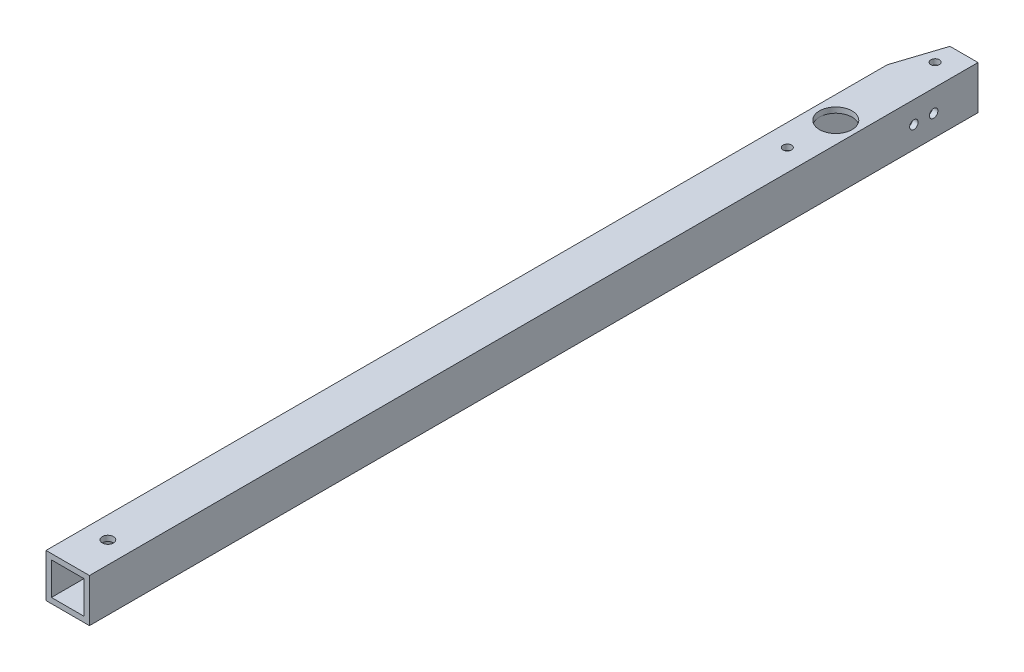
SolidWorks part; units mm, degrees
ref_plane "Front Plane" through (0, 0, 0) normal (0, 0, 1) x (1, 0, 0)
ref_plane "Top Plane" through (0, 0, 0) normal (0, 1, 0) x (1, 0, 0)
ref_plane "Right Plane" through (0, 0, 0) normal (1, 0, 0) x (0, 0, -1)
sketch "Sketch1" plane through (0, 0, 0) normal (0, 0, 1) x (1, 0, 0)
  line L0 (-9.525, 9.525) -> (9.525, 9.525)
  line L2 (-12.7, 12.7) -> (12.7, 12.7)
  line L3 (-12.7, 12.7) -> (-12.7, -12.7)
  line L4 (-12.7, -12.7) -> (12.7, -12.7)
  line L5 (12.7, 12.7) -> (12.7, -12.7)
  line L10 (9.525, 9.525) -> (9.525, -9.525)
  line L11 (-9.525, -9.525) -> (9.525, -9.525)
  line L12 (-9.525, 9.525) -> (-9.525, -9.525)
  point P12 (0, 12.7)
  point P14 (12.7, 0)
  dimension "Wall Thickness" = 3.175
  dimension "Outside Width" = 25.4
  dimension "Outside Height" = 25.4
  dimension "Inside Height" = 19.05
  dimension "Inside Width" = 19.05
sketch "Sketch2" plane through (0, 0, 0) normal (1, 0, 0) x (0, 0, -1)
  line L0 (266.7, 0) -> (-266.7, 0)
  point P4 (0, 0)
  point P7 (-266.7, 0)
  point P10 (266.7, 0)
  dimension "Length" = 533.4
sketch "Sketch3" plane through (0, 0, 0) normal (0, 0, 1) x (1, 0, 0)
  line L21 (12.7, 12.7) -> (-12.7, 12.7)
  line L22 (12.7, -12.7) -> (12.7, 12.7)
  line L23 (-12.7, -12.7) -> (12.7, -12.7)
  line L24 (-12.7, 12.7) -> (-12.7, -12.7)
  line L25 (12.7, 12.7) -> (-12.7, 12.7)
  line L26 (12.7, -12.7) -> (12.7, 12.7)
  line L27 (-12.7, -12.7) -> (12.7, -12.7)
  line L28 (-12.7, 12.7) -> (-12.7, -12.7)
  line L29 (9.525, 9.525) -> (-9.525, 9.525)
  line L30 (9.525, -9.525) -> (9.525, 9.525)
  line L31 (-9.525, -9.525) -> (9.525, -9.525)
  line L32 (-9.525, 9.525) -> (-9.525, -9.525)
  line L33 (9.525, 9.525) -> (-9.525, 9.525)
  line L34 (9.525, -9.525) -> (9.525, 9.525)
  line L35 (-9.525, -9.525) -> (9.525, -9.525)
  line L36 (-9.525, 9.525) -> (-9.525, -9.525)
  dimension "D1" = 0
  dimension "D2" = 0
extrude "Boss-Extrude1" add sketch "Sketch3" along normal up to vertex (266.7 mm away) and the other way up to vertex (266.7 mm away) up to point (0, 0, 266.7) other way up to point (0, 0, -266.7)
sketch "Drawing Reference" plane through (0, 0, 0) normal (1, 0, 0) x (0, 0, -1)
  line L0 (-266.7, 0) -> (266.7, 0) construction
  line L1 (0, -12.7) -> (0, 12.7) construction
  line L2 (-266.7, -12.7) -> (266.7, -12.7) construction
  line L5 (-266.7, 12.7) -> (266.7, 12.7) construction
  point P7 (-248.412, 0)
  point P8 (248.412, 0)
  dimension "D1" = 18.288
sketch "Sketch4" plane through (0, 12.7, 0) normal (0, 1, 0) x (1, 0, 0)
  line L7 (-12.7, 225.0135) -> (-12.7, 266.7)
  line L8 (-188.9197, -317.3351) -> (4.6184, 278.3139) construction
  line L10 (-12.7, -266.7) -> (-12.7, 266.7) construction
  line L11 (-12.7, 266.7) -> (12.7, 266.7)
  line L12 (12.7, 266.7) -> (12.7, 252.73)
  line L13 (12.7, -266.7) -> (12.7, 266.7) construction
  line L14 (12.7, 252.73) -> (-3.6943, 252.73)
  line L15 (-3.6943, 252.73) -> (-12.7, 225.0135)
  dimension "D1" = 13.97
extrude "Cut-Extrude1" cut sketch "Sketch4" against normal blind 25.4
sketch "Sketch5" plane through (0, 12.7, 0) normal (0, -1, 0) x (1, 0, 0)
  circle A0 centre (0.3539, -181.928) radius 9.525
extrude "Cut-Extrude2" cut sketch "Sketch5" along normal blind 3.175
sketch "Sketch6" plane through (12.7, 0, 0) normal (1, 0, 0) x (0, 0, -1)
  line L0 (252.73, 0) -> (215.265, 0) construction
  line L1 (252.73, -12.7) -> (252.73, 12.7) construction
  line L2 (215.265, 0) -> (227.965, 0) construction
  dimension "D1" = 37.465
hole_wizard "#10 Clearance Hole2" positions "Sketch9" profile "Sketch10" hole size "#10" standard "ANSI Inch" end condition through all
sketch "Sketch9" plane through (0, -12.7, 0) normal (0, -1, 0) x (-1, 0, 0)
  point P0 (0, 153.96)
  point P3 (0, 240.3465)
sketch "Sketch10" plane through (0, -12.7, -153.96) normal (1, 0, 0) x (0, 0, -1)
  line L0 (0, 0) -> (0, 25.4)
  line L1 (0, 25.4) -> (2.4892, 25.4)
  line L2 (2.4892, 25.4) -> (2.4892, 0)
  line L5 (2.4892, 0) -> (0, 0)
  line L11 (0, -6.35) -> (0, 107.95) construction
  dimension "Thru Hole Dia." = 4.9784
  dimension "Thru Hole Depth" = 25.4
hole_wizard "1/4 Clearance Hole1" positions "Sketch11" profile "Sketch12" hole size "1/4" standard "ANSI Inch" end condition through all
sketch "Sketch11" plane through (0, -12.7, 0) normal (0, -1, 0) x (-1, 0, 0)
  point P0 (0, -243.2272)
sketch "Sketch12" plane through (0, -12.7, 243.2272) normal (1, 0, 0) x (0, 0, -1)
  line L0 (0, 0) -> (0, 25.4)
  line L1 (0, 25.4) -> (3.2639, 25.4)
  line L2 (3.2639, 25.4) -> (3.2639, 0)
  line L5 (3.2639, 0) -> (0, 0)
  line L11 (0, -6.35) -> (0, 107.95) construction
  dimension "Thru Hole Dia." = 6.5278
  dimension "Thru Hole Depth" = 25.4
hole_wizard "#10 Clearance Hole3" positions "Sketch13" profile "Sketch14" hole size "#10" standard "ANSI Inch"
sketch "Sketch13" plane through (12.7, 0, 0) normal (1, 0, 0) x (0, 0, -1)
  point P0 (226.7882, -0.0596)
  point P4 (215.265, 0)
sketch "Sketch14" plane through (12.7, -0.0596, -226.7882) normal (0, 1, 0) x (0, 0, -1)
  line L0 (0, 0) -> (0, 6.5757)
  line L1 (0, 6.5757) -> (2.4892, 5.08)
  line L2 (2.4892, 5.08) -> (2.4892, 0)
  line L5 (2.4892, 0) -> (0, 0)
  line L10 (0, 6.5757) -> (-2.4892, 5.08) construction
  line L11 (0, -6.35) -> (0, 107.95) construction
  dimension "Hole Dia." = 4.9784
  dimension "Hole Depth" = 5.08
  dimension "Drill Angle" = 118
equation "\"D1@Drawing Reference\"=\"Outside Width@Sketch1\" * 0.72"
